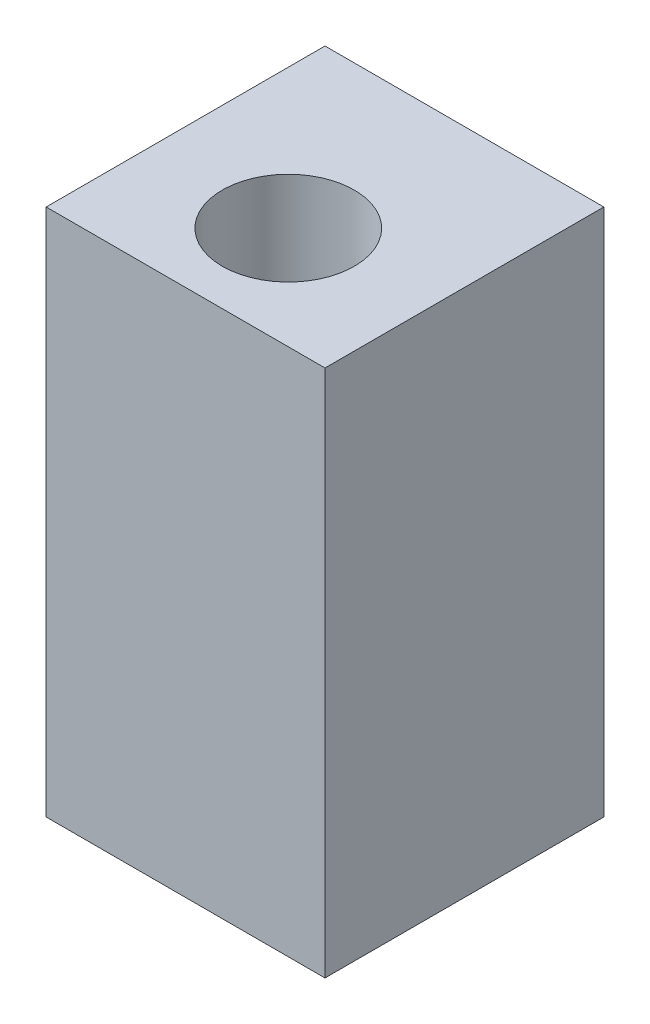
SolidWorks part; units mm, degrees
ref_plane "Front Plane" through (0, 0, 0) normal (0, 0, 1) x (1, 0, 0)
ref_plane "Top Plane" through (0, 0, 0) normal (0, 1, 0) x (1, 0, 0)
ref_plane "Right Plane" through (0, 0, 0) normal (1, 0, 0) x (0, 0, -1)
sketch "Sketch2" plane through (0, 0, 0) normal (0, 1, 0) x (1, 0, 0)
  line L1 (-4.75, 4.75) -> (4.75, 4.75)
  line L2 (-4.75, 4.75) -> (-4.75, -4.75)
  line L3 (-4.75, -4.75) -> (4.75, -4.75)
  line L4 (4.75, 4.75) -> (4.75, -4.75)
  line L5 (-4.75, 4.75) -> (4.75, -4.75) construction
  line L6 (-4.75, -4.75) -> (4.75, 4.75) construction
  point P0 (0, 0)
  dimension "D1" = 9.5
  dimension "D2" = 9.5
extrude "Boss-Extrude1" add sketch "Sketch2" along normal blind 18
sketch "Sketch3" plane through (0, 18, 0) normal (0, 1, 0) x (1, 0, 0)
  line L1 (-4.75, 4.75) -> (4.75, 4.75)
  line L2 (-4.75, 4.75) -> (-4.75, -4.75)
  line L3 (-4.75, -4.75) -> (4.75, -4.75)
  line L4 (4.75, 4.75) -> (4.75, -4.75)
  line L5 (-4.75, 4.75) -> (4.75, -4.75) construction
  line L6 (-4.75, -4.75) -> (4.75, 4.75) construction
  circle A0 centre (0, -1.25) radius 2.25
  point P0 (0, 0)
  dimension "D1" = 3.5
extrude "Cut-Extrude1" cut sketch "Sketch3" against normal blind 21 contours A0
